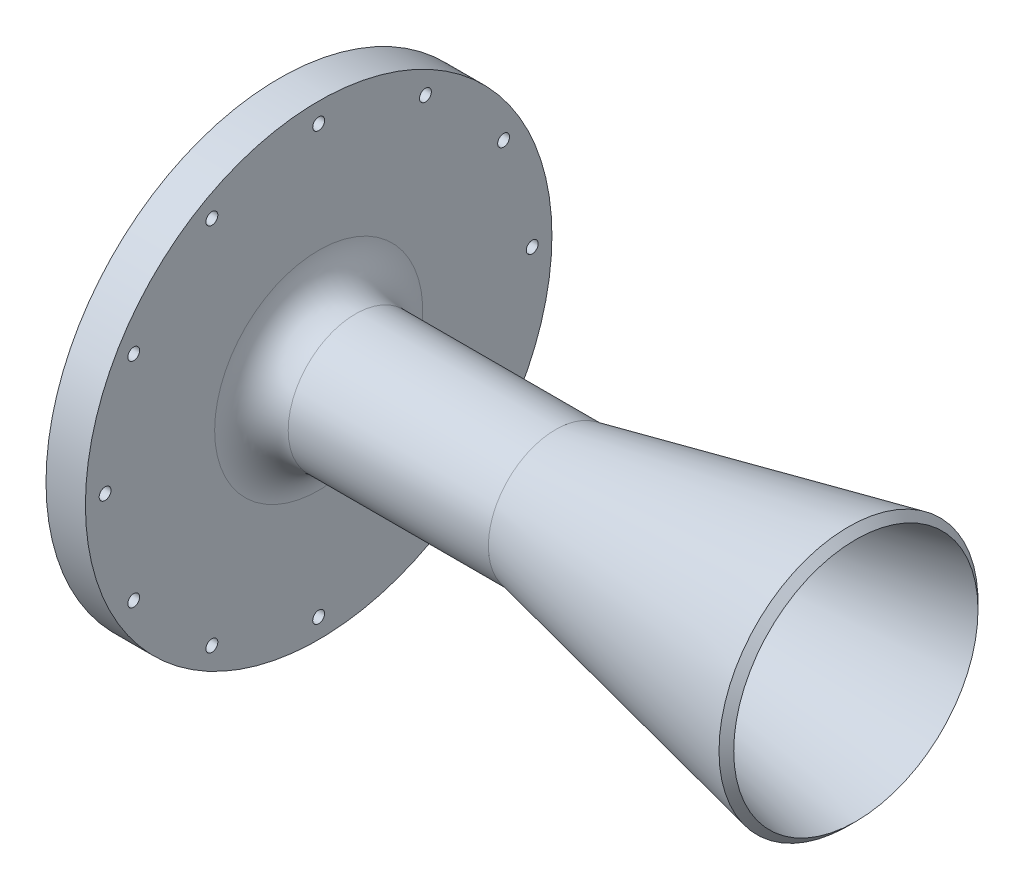
SolidWorks part; units mm, degrees
material "Stainless Steel (ferritic)"
ref_plane "Front Plane" through (0, 0, 0) normal (0, 0, 1) x (1, 0, 0)
ref_plane "Top Plane" through (0, 0, 0) normal (0, 1, 0) x (1, 0, 0)
ref_plane "Right Plane" through (0, 0, 0) normal (1, 0, 0) x (0, 0, -1)
sketch "Sketch2" plane through (0, 0, 0) normal (0, 0, 1) x (1, 0, 0)
  line L0 (0, 0) -> (165.0115, 0) construction
  line L1 (0, 20.5835) -> (0, 56.388)
  line L2 (0, 56.388) -> (9.525, 56.388)
  line L3 (9.525, 56.388) -> (9.525, 16.256)
  line L11 (66.8065, 16.256) -> (139.7, 31.75)
  line L17 (139.7, 31.75) -> (139.7, 29.5925)
  line L18 (60.325, 12.7208) -> (60.325, 14.351)
  line L19 (60.325, 14.351) -> (10.795, 14.351)
  line L20 (0, 20.5835) -> (10.795, 14.351)
  line L21 (60.325, 12.7208) -> (139.7, 29.5925)
  line L22 (9.525, 16.256) -> (66.8065, 16.256)
  dimension "D2" = 9.525
  dimension "D3" = 1.905
  dimension "D4" = 10.795
  dimension "D5" = 14.351
  dimension "D6" = 31.75
  dimension "D7" = 12
  dimension "D8" = 139.7
  dimension "D9" = 1.6302
  dimension "D10" = 30
  dimension "D11" = 56.388
  dimension "D12" = 49.53
revolve "Main Structure" add sketch "Sketch2" angle 360 about L0
sketch "Sketch4" plane through (0, 0, 0) normal (-1, 0, 0) x (0, 0, 1)
  circle A0 centre (0, 0) radius 51.6255 construction
  circle A1 centre (0, -51.6255) radius 2.146
  circle A2 centre (-25.8127, -44.709) radius 2.146
  circle A3 centre (-44.709, -25.8128) radius 2.146
  circle A4 centre (-51.6255, 0) radius 2.146
  circle A5 centre (-44.709, 25.8127) radius 2.146
  circle A6 centre (-25.8128, 44.709) radius 2.146
  circle A7 centre (0, 51.6255) radius 2.146
  circle A8 centre (25.8127, 44.709) radius 2.146
  circle A9 centre (44.709, 25.8128) radius 2.146
  circle A10 centre (51.6255, 0) radius 2.146
  circle A11 centre (44.709, -25.8127) radius 2.146
  circle A12 centre (25.8128, -44.709) radius 2.146
  point P29 (0, 0)
  dimension "D1" = 12
  dimension "D2" = 103.251
hole_wizard "Flange Holes" positions "Sketch7" profile "Sketch8" hole size "#33" standard "ANSI Inch" end condition up to next
sketch "Sketch7" plane through (0, 0, 0) normal (-1, 0, 0) x (0, 0, 1)
  point P0 (0, -51.6255)
  point P3 (-25.8127, -44.709)
  point P6 (-44.709, -25.8128)
  point P9 (-51.6255, 0)
  point P12 (-44.709, 25.8127)
  point P15 (-25.8128, 44.709)
  point P18 (0, 51.6255)
  point P21 (25.8127, 44.709)
  point P24 (44.709, 25.8128)
  point P27 (51.6255, 0)
  point P30 (44.709, -25.8127)
  point P33 (25.8128, -44.709)
sketch "Sketch8" plane through (0, -51.6255, 0) normal (0, 1, 0) x (0, 0, 1)
  line L0 (0, 0) -> (0, 9.525)
  line L1 (0, 9.525) -> (1.4351, 9.525)
  line L2 (1.4351, 9.525) -> (1.4351, 0)
  line L5 (1.4351, 0) -> (0, 0)
  line L11 (0, -6.35) -> (0, 107.95) construction
  dimension "Thru Hole Dia." = 2.8702
  dimension "Thru Hole Depth" = 9.525
sketch "Sketch9" plane through (0, 0, 0) normal (-1, 0, 0) x (0, 0, 1)
  line L0 (0, 0) -> (-67.6727, 18.1329) construction
  line L1 (0, 0) -> (-51.6255, 0) construction
  circle A0 centre (0, 0) radius 51.6255 construction
  circle A1 centre (-49.8664, 13.3617) radius 2.9451
  circle A2 centre (49.8664, -13.3617) radius 2.9451
  point P14 (0, 0)
  dimension "D1" = 15
  dimension "D2" = 2
hole_wizard "Dowel Holes" positions "Sketch10" profile "Sketch11" hole size "3/16" standard "ANSI Inch"
sketch "Sketch10" plane through (0, 0, 0) normal (-1, 0, 0) x (0, 0, 1)
  point P0 (49.8664, -13.3617)
  point P3 (-49.8664, 13.3617)
sketch "Sketch11" plane through (0, -13.3617, 49.8664) normal (0, 1, 0) x (0, 0, 1)
  line L0 (0, 0) -> (0, 7.7808)
  line L1 (0, 7.7808) -> (2.3812, 6.35)
  line L2 (2.3812, 6.35) -> (2.3812, 0)
  line L5 (2.3812, 0) -> (0, 0)
  line L10 (0, 7.7808) -> (-2.3812, 6.35) construction
  line L11 (0, -6.35) -> (0, 107.95) construction
  dimension "Hole Dia." = 4.7625
  dimension "Hole Depth" = 6.35
  dimension "Drill Angle" = 118
fillet "Fillet1" radius 8.89 1 edges at (9.525, 0, 16.256)
sketch "Sketch13" plane through (0, 0, 0) normal (0, 1, 0) x (1, 0, 0)
  line L0 (0, 36) -> (3.1496, 0)
  line L1 (0, 56.388) -> (0, -56.388) construction
  line L2 (3.1496, 0) -> (0, 0)
  line L3 (0, 0) -> (0, 36)
  dimension "D1" = 36
  dimension "D2" = 5
revolve "Cut-Revolve1" cut sketch "Sketch13" angle 360 about L2
chamfer "Chamfer1" distance 2.54 angle 45 1 edges at (139.7, 0, 31.75) first distance on face at (139.7, 0, 31.75)
